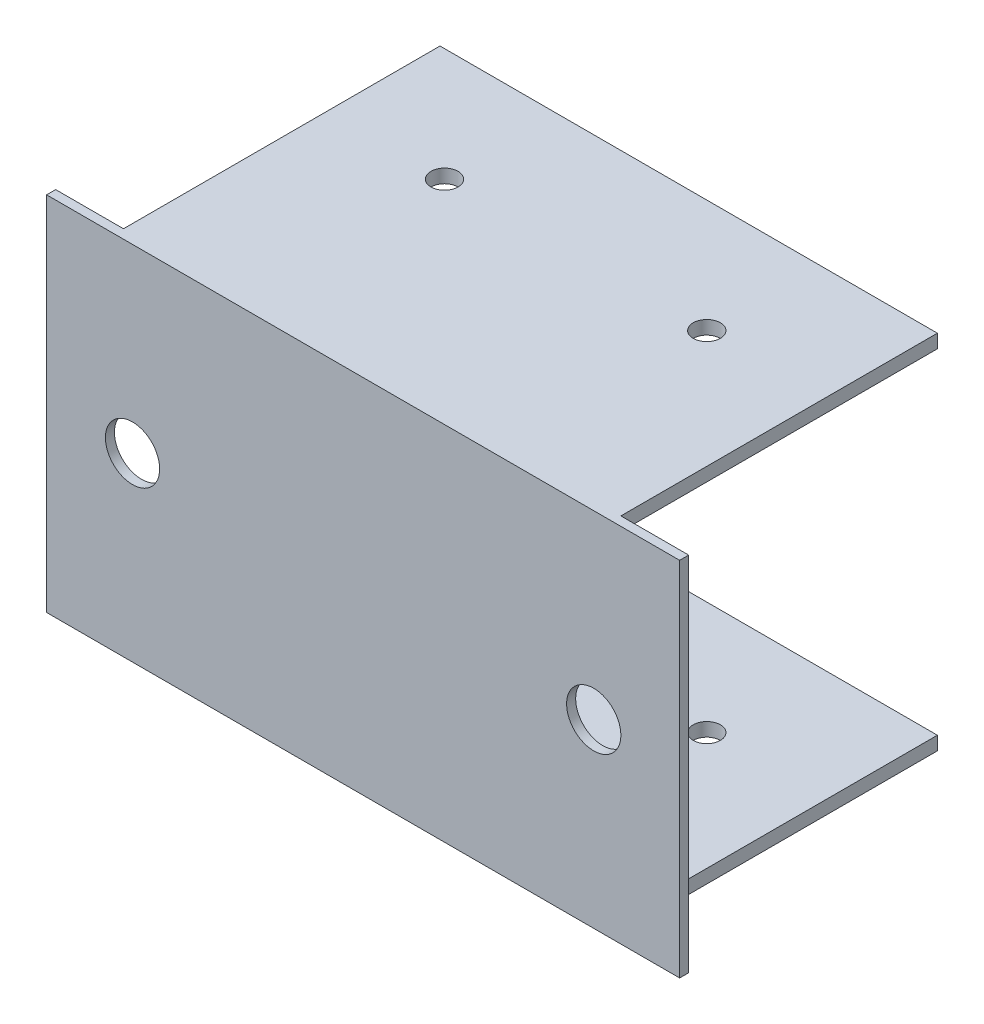
SolidWorks part; units mm, degrees
ref_plane "前视基准面" through (0, 0, 0) normal (0, 0, 1) x (1, 0, 0)
ref_plane "上视基准面" through (0, 0, 0) normal (0, 1, 0) x (1, 0, 0)
ref_plane "右视基准面" through (0, 0, 0) normal (1, 0, 0) x (0, 0, -1)
sketch "草图1" plane through (0, 0, 0) normal (0, 0, 1) x (1, 0, 0)
  line L1 (-35, 20) -> (35, 20)
  line L2 (-35, 20) -> (-35, -20)
  line L3 (-35, -20) -> (35, -20)
  line L4 (35, 20) -> (35, -20)
  line L5 (-35, 20) -> (35, -20) construction
  line L6 (-35, -20) -> (35, 20) construction
  point P0 (0, 0)
  dimension "D1" = 70
  dimension "D2" = 40
extrude "凸台-拉伸1" add sketch "草图1" along normal blind 1 contours L2 L3 L4 L1
sketch "草图2" plane through (0, 0, 1) normal (0, 0, 1) x (1, 0, 0)
  line L0 (-25.5, 0) -> (25.5, 0) construction
  circle A0 centre (-25.5, 0) radius 3
  circle A1 centre (25.5, 0) radius 3
  point P2 (0, 0)
  dimension "D2" = 6
  dimension "D3" = 6
  dimension "D1" = 51
extrude "切除-拉伸1" cut sketch "草图2" against normal blind 10
sketch "草图4" plane through (0, 20, 0) normal (0, 1, 0) x (1, 0, 0)
  line L0 (-35, -1) -> (35, -1) construction
  line L1 (-27.5, 35) -> (27.5, 35)
  line L2 (-27.5, 35) -> (-27.5, -1)
  line L3 (-27.5, -1) -> (27.5, -1)
  line L4 (27.5, 35) -> (27.5, -1)
  line L5 (-27.5, 35) -> (27.5, -1) construction
  line L6 (-27.5, -1) -> (27.5, 35) construction
  point P0 (0, 17)
  dimension "D1" = 36
  dimension "D2" = 55
extrude "凸台-拉伸2" add sketch "草图4" against normal blind 1.5
extrude "凸台-拉伸3" add sketch "草图4<2>" along normal blind 1.5 from offset 40 offset against normal yes
sketch "草图4<2>" plane through (0, 20, 0) normal (0, 1, 0) x (1, 0, 0) same geometry as "草图4"
sketch "草图5" plane through (0, 20, 0) normal (0, 1, 0) x (1, 0, 0)
  line L0 (-14.5, 22.5) -> (14.5, 22.5) construction
  line L1 (27.5, 35) -> (-27.5, 35) construction
  circle A0 centre (-14.5, 22.5) radius 1.5
  circle A1 centre (14.5, 22.5) radius 1.5
  point P2 (0, 22.5)
  dimension "D3" = 3
  dimension "D4" = 3
  dimension "D1" = 12.5
  dimension "D2" = 29
extrude "切除-拉伸2" cut sketch "草图5" against normal through all
